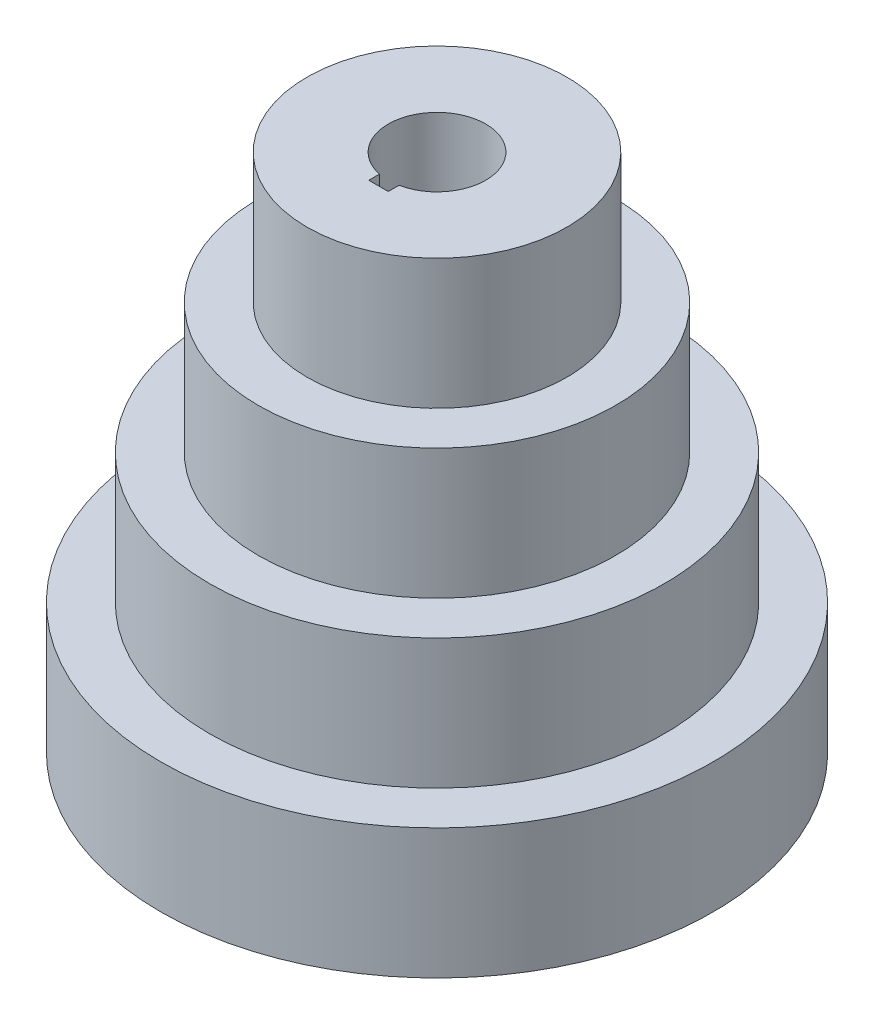
SolidWorks part; units mm, degrees
ref_plane "Front Plane" through (0, 0, 0) normal (0, 0, 1) x (1, 0, 0)
ref_plane "Top Plane" through (0, 0, 0) normal (0, 1, 0) x (1, 0, 0)
ref_plane "Right Plane" through (0, 0, 0) normal (1, 0, 0) x (0, 0, -1)
sketch "Sketch1" plane through (0, 0, 0) normal (0, 1, 0) x (1, 0, 0)
  circle A0 centre (0, 0) radius 85
extrude "Boss-Extrude1" add sketch "Sketch1" along normal blind 40
sketch "Sketch2" plane through (0, 40, 0) normal (0, 1, 0) x (1, 0, 0)
  circle A0 centre (0, 0) radius 70
extrude "Boss-Extrude2" add sketch "Sketch2" along normal blind 40
sketch "Sketch3" plane through (0, 80, 0) normal (0, 1, 0) x (1, 0, 0)
  circle A0 centre (0, 0) radius 55
extrude "Boss-Extrude3" add sketch "Sketch3" along normal blind 40
sketch "Sketch4" plane through (0, 120, 0) normal (0, 1, 0) x (1, 0, 0)
  circle A0 centre (0, 0) radius 40
  point P3 (-50.0874, 14.1242)
extrude "Boss-Extrude4" add sketch "Sketch4" along normal blind 40
sketch "Sketch5" plane through (0, 160, 0) normal (0, 1, 0) x (1, 0, 0)
  line L1 (-3, -18) -> (3, -18)
  line L2 (-3, -18) -> (-3, -12)
  line L3 (-3, -12) -> (3, -12)
  line L4 (3, -18) -> (3, -12)
  line L5 (-3, -18) -> (3, -12) construction
  line L6 (-3, -12) -> (3, -18) construction
  circle A0 centre (0, 0) radius 15
  point P3 (0, -15)
  dimension "D1" = 6
  dimension "D2" = 6
extrude "Cut-Extrude1" cut sketch "Sketch5" against normal through all contours L4 A0 L2 L3 | L1 L4 L3 L2 region at (0, 160, -0.3394)
shell "Shell1" thickness 10 removed face at (0, 0, 8.9242)
